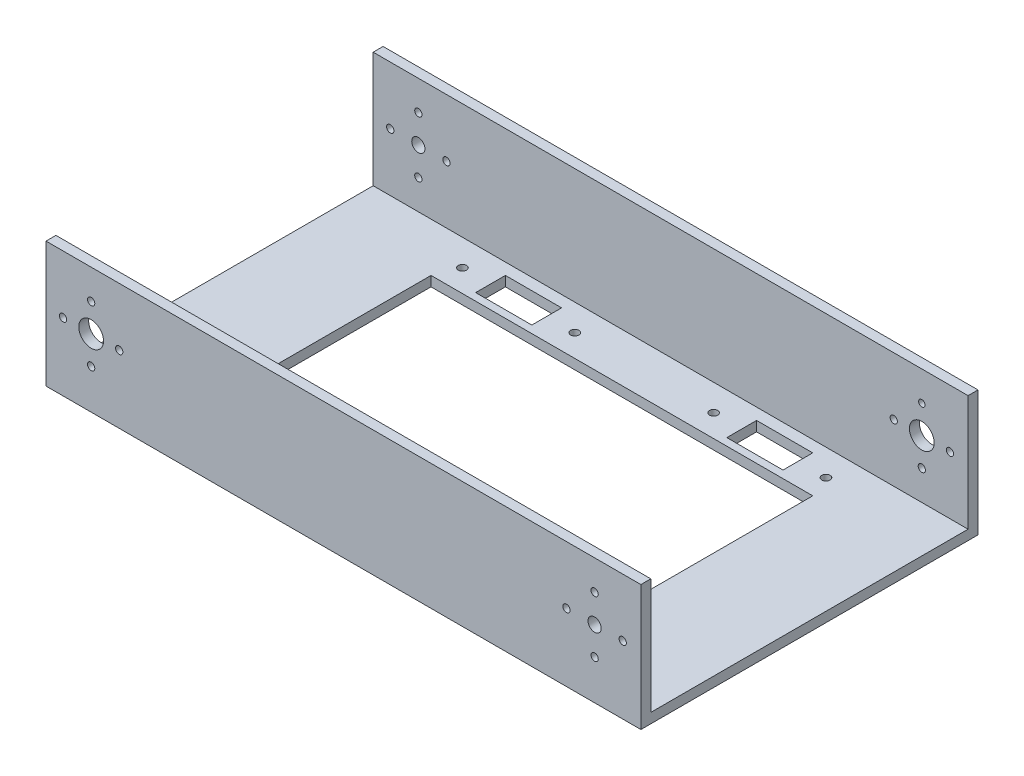
SolidWorks part; units mm, degrees
ref_plane "Front Plane" through (0, 0, 0) normal (0, 0, 1) x (1, 0, 0)
ref_plane "Top Plane" through (0, 0, 0) normal (0, 1, 0) x (1, 0, 0)
ref_plane "Right Plane" through (0, 0, 0) normal (1, 0, 0) x (0, 0, -1)
sketch "스케치1" plane through (0, 0, 0) normal (0, 0, 1) x (1, 0, 0)
  line L1 (-90, 17.5) -> (90, 17.5)
  line L2 (-90, 17.5) -> (-90, -17.5)
  line L3 (-90, -17.5) -> (90, -17.5)
  line L4 (90, 17.5) -> (90, -17.5)
  dimension "D1" = 17.5
  dimension "D2" = 35
  dimension "D3" = 90
  dimension "D4" = 180
extrude "보스-돌출1" add sketch "스케치1" along normal blind 3
sketch "스케치2" plane through (0, 0, 3) normal (0, 0, 1) x (1, 0, 0)
  line L0 (0, 0) -> (50000, 0) construction
  line L1 (0, 0) -> (0, -50000) construction
  line L2 (-76, 0) -> (-76, -50000) construction
  line L3 (76, 0) -> (76, -50000) construction
  circle A0 centre (-76.34, 0) radius 3.75
  circle A1 centre (76, 0) radius 2
  dimension "D3" = 7.5
  dimension "D4" = 4
  dimension "D1" = 76
  dimension "D2" = 76
extrude "컷-돌출1" cut sketch "스케치2" against normal blind 3
sketch "스케치3" plane through (0, 0, 3) normal (0, 0, 1) x (1, 0, 0)
  line L0 (-76.34, 0) -> (-76.34, 50000) construction
  line L1 (76, 0) -> (76, 50000) construction
  line L2 (-76.34, 0) -> (49923.66, 0) construction
  circle A0 centre (-76.34, 0) radius 8.5 construction
  circle A1 centre (76, 0) radius 8.5 construction
  circle A2 centre (-76.34, 8.5) radius 1.1
  circle A3 centre (-76.34, -8.5) radius 1.1
  circle A4 centre (-84.84, 0) radius 1.1
  circle A5 centre (-67.84, 0) radius 1.1
  circle A6 centre (76, 8.5) radius 1.1
  circle A7 centre (76, -8.5) radius 1.1
  circle A8 centre (67.5, 0) radius 1.1
  circle A9 centre (84.5, 0) radius 1.1
extrude "컷-돌출2" cut sketch "스케치3" against normal blind 3
sketch "스케치4" plane through (0, -17.5, 0) normal (0, -1, 0) x (1, 0, 0)
  line L0 (-90, 0) -> (-90, 50000) construction
  line L1 (90, 0) -> (90, 50000) construction
  line L2 (-100, 3) -> (49900, 3) construction
  line L6 (-100, -96) -> (49900, -96) construction
  line L7 (-100, -99) -> (49900, -99) construction
  line L8 (-100, 0) -> (49900, 0) construction
  line L11 (90, 3) -> (-90, 3)
  line L12 (90, 3) -> (90, -99)
  line L13 (90, -99) -> (-90, -99)
  line L14 (-90, 3) -> (-90, -99)
  dimension "D1" = 3
  dimension "D2" = 96
extrude "보스-돌출2" add sketch "스케치4" along normal blind 3
sketch "스케치5" plane through (0, -17.5, 0) normal (0, 1, 0) x (1, 0, 0)
  line L0 (-100, 99) -> (49900, 99) construction
  line L1 (86.532, 96) -> (50086.532, 96) construction
  line L2 (-90, 0) -> (-90, 50000) construction
  line L3 (-90, 0) -> (-90, 99) construction
  line L4 (90, 0) -> (90, 50000) construction
  line L7 (-90, 99) -> (90, 99)
  line L8 (-90, 99) -> (-90, 96)
  line L9 (-90, 96) -> (90, 96)
  line L10 (90, 99) -> (90, 96)
  dimension "D1" = 3
extrude "보스-돌출3" add sketch "스케치5" along normal blind 35
sketch "스케치6" plane through (0, 0, -99) normal (0, 0, -1) x (-1, 0, 0)
  circle A0 centre (-76, 0) radius 3.75
  circle A1 centre (76.34, 0) radius 2
  circle A2 centre (-76, -8.5) radius 1.1
  circle A3 centre (-67.5, 0) radius 1.1
  circle A4 centre (-76, 8.5) radius 0.9817
  circle A5 centre (-84.5, 0) radius 1.1
  circle A6 centre (84.84, 0) radius 1.1
  circle A7 centre (76.34, 8.5) radius 1.1
  circle A8 centre (67.84, 0) radius 1.1
  circle A9 centre (76.34, -8.5) radius 1.1
  dimension "D1" = 4
extrude "컷-돌출3" cut sketch "스케치6" against normal blind 35
sketch "스케치9" plane through (0, -17.5, 0) normal (0, 1, 0) x (1, 0, 0)
  line L0 (-0.8224, 48) -> (49999.1776, 48) construction
  line L1 (0, 0) -> (0, 50000) construction
  line L2 (90, 0) -> (-90, 0) construction
  line L4 (-57.75, 81.25) -> (57.75, 81.25)
  line L5 (-57.75, 81.25) -> (-57.75, 14.75)
  line L6 (-57.75, 14.75) -> (57.75, 14.75)
  line L7 (57.75, 81.25) -> (57.75, 14.75)
  dimension "D1" = 48
  dimension "D2" = 66.5
  dimension "D3" = 115.5
  dimension "D4" = 57.75
  dimension "D5" = 33.25
extrude "컷-돌출4" cut sketch "스케치9" against normal blind 10
sketch "스케치10" plane through (0, -20.5, 0) normal (0, -1, 0) x (1, 0, 0)
  line L0 (-10.9491, -48) -> (49989.0509, -48) construction
  line L1 (0, -34.9167) -> (0, -50034.9167) construction
  line L2 (-55, -10.9771) -> (-55, -50010.9771) construction
  line L3 (55, 8.1375) -> (55, -49991.8625) construction
  line L4 (-54.3745, -8) -> (49945.6255, -8) construction
  line L5 (75.9016, -88) -> (50075.9016, -88) construction
  line L6 (-90, 3) -> (-90, -99) construction
  line L7 (-90, -96) -> (90, -96) construction
  circle A0 centre (-55, -8) radius 1.25
  circle A1 centre (55, -8) radius 1.25
  circle A2 centre (55, -88) radius 1.25
  circle A3 centre (-55, -88) radius 1.25
  dimension "D1" = 90
  dimension "D2" = 48
  dimension "D3" = 55
  dimension "D4" = 55
  dimension "D5" = 40
  dimension "D6" = 40
extrude "컷-돌출5" cut sketch "스케치10" against normal blind 10
sketch "스케치11" plane through (0, -20.5, 0) normal (0, -1, 0) x (1, 0, 0)
  line L0 (55, -8) -> (-49945, -8) construction
  line L1 (55, -8) -> (55, -50008) construction
  line L2 (-55, -88) -> (-55, 49912) construction
  line L3 (-55, -88) -> (49945, -88) construction
  line L4 (38, -39.7065) -> (38, -50039.7065) construction
  line L5 (-38, -46.9547) -> (-38, -50046.9547) construction
  line L6 (21, -25.4517) -> (21, -50025.4517) construction
  line L7 (-21, -44.297) -> (-21, -50044.297) construction
  line L9 (46.5, -83.5) -> (29.5, -83.5)
  line L10 (46.5, -83.5) -> (46.5, -92.5)
  line L11 (46.5, -92.5) -> (29.5, -92.5)
  line L12 (29.5, -83.5) -> (29.5, -92.5)
  line L13 (-29.5, -83.5) -> (-46.5, -83.5)
  line L14 (-29.5, -83.5) -> (-29.5, -92.5)
  line L15 (-29.5, -92.5) -> (-46.5, -92.5)
  line L16 (-46.5, -83.5) -> (-46.5, -92.5)
  line L17 (46.5, -3.5) -> (29.5, -3.5)
  line L18 (46.5, -3.5) -> (46.5, -12.5)
  line L19 (46.5, -12.5) -> (29.5, -12.5)
  line L20 (29.5, -3.5) -> (29.5, -12.5)
  line L21 (-29.5, -3.5) -> (-46.5, -3.5)
  line L22 (-29.5, -3.5) -> (-29.5, -12.5)
  line L23 (-29.5, -12.5) -> (-46.5, -12.5)
  line L24 (-46.5, -3.5) -> (-46.5, -12.5)
  circle A0 centre (21, -8) radius 1.25
  circle A1 centre (-21, -8) radius 1.25
  circle A2 centre (21, -88) radius 1.25
  circle A3 centre (-21, -88) radius 1.25
  dimension "D5" = 17
  dimension "D1" = 17
  dimension "D2" = 17
  dimension "D3" = 17
  dimension "D4" = 17
  dimension "D6" = 9
  dimension "D7" = 9
  dimension "D8" = 17
  dimension "D9" = 17
  dimension "D10" = 9
  dimension "D11" = 17
  dimension "D12" = 9
  dimension "D13" = 8.5
  dimension "D14" = 4.5
  dimension "D15" = 4.5
  dimension "D16" = 8.5
  dimension "D17" = 4.5
  dimension "D18" = 8.5
  dimension "D19" = 8.5
  dimension "D20" = 4.5
extrude "컷-돌출6" cut sketch "스케치11" against normal blind 10
